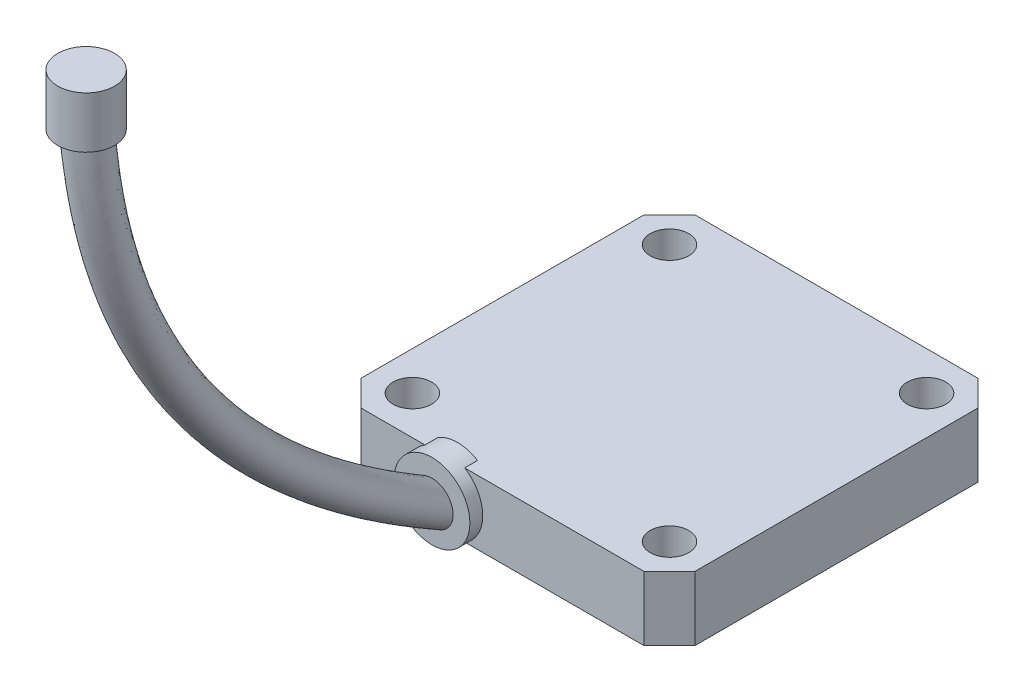
SolidWorks part; units mm, degrees
ref_plane "Front Plane" through (0, 0, 0) normal (0, 0, 1) x (1, 0, 0)
ref_plane "Top Plane" through (0, 0, 0) normal (0, 1, 0) x (1, 0, 0)
ref_plane "Right Plane" through (0, 0, 0) normal (1, 0, 0) x (0, 0, -1)
sketch "Sketch1" plane through (0, 0, 0) normal (0, 1, 0) x (1, 0, 0)
  line L0 (-11, 13) -> (-13, 11)
  line L1 (11, -13) -> (-11, -13)
  line L2 (13, -11) -> (13, 11)
  line L3 (11, 13) -> (-11, 13)
  line L4 (-13, -11) -> (-13, 11)
  line L5 (13, -13) -> (-13, 13) construction
  line L6 (13, 13) -> (-13, -13) construction
  line L7 (10, -10) -> (-10, -10) construction
  line L8 (10, -10) -> (10, 10) construction
  line L9 (10, 10) -> (-10, 10) construction
  line L10 (-10, -10) -> (-10, 10) construction
  line L11 (10, -10) -> (-10, 10) construction
  line L12 (10, 10) -> (-10, -10) construction
  line L13 (13, 11) -> (11, 13)
  line L14 (13, -11) -> (11, -13)
  line L15 (-11, -13) -> (-13, -11)
  circle A0 centre (-10, 10) radius 1.5
  circle A1 centre (10, 10) radius 1.5
  circle A2 centre (10, -10) radius 1.5
  circle A3 centre (-10, -10) radius 1.5
  point P0 (0, 0)
  point P6 (0, 0)
  dimension "D1" = 26
  dimension "D2" = 26
  dimension "D3" = 20
  dimension "D4" = 20
extrude "Boss-Extrude1" add sketch "Sketch1" along normal blind 5
sketch "Sketch2" plane through (0, 0, 13) normal (0, 0, 1) x (1, 0, 0)
  circle A1 centre (-4.4763, 2.4862) radius 2.9503
extrude "Boss-Extrude2" add sketch "Sketch2" along normal mid plane 2
sketch "Sketch3" plane through (0, 0, 14) normal (0, 0, 1) x (1, 0, 0)
  circle A0 centre (-4.4763, 2.3895) radius 1.6452
sketch "Sketch25" plane through (0, 0, 0) normal (1, 0, 0) x (0, 0, -1)
  line L0 (-14, 4.0346) -> (-14, 0.7443) construction
  spline S0 degree 2 poles (-14, 2.3895) (-39.1923, 16.8936) (-40.9005, 42.0027) knots 0 0 0 1 1 1
  point P2 (-14, 2.3895)
  point P4 (-39.5096, 33.2484)
  point P5 (-40.9005, 42.0027)
sweep "Sweep5" add profiles "Sketch3" path "Sketch25"
ref_plane "Plane2" through (0, 45, 0) normal (0, 1, 0) x (1, 0, 0)
sketch "Sketch30" plane through (0, 45, 0) normal (0, 1, 0) x (1, 0, 0)
  circle A0 centre (-4.4763, -40.9005) radius 2.2104
extrude "Boss-Extrude4" add sketch "Sketch30" against normal blind 4
